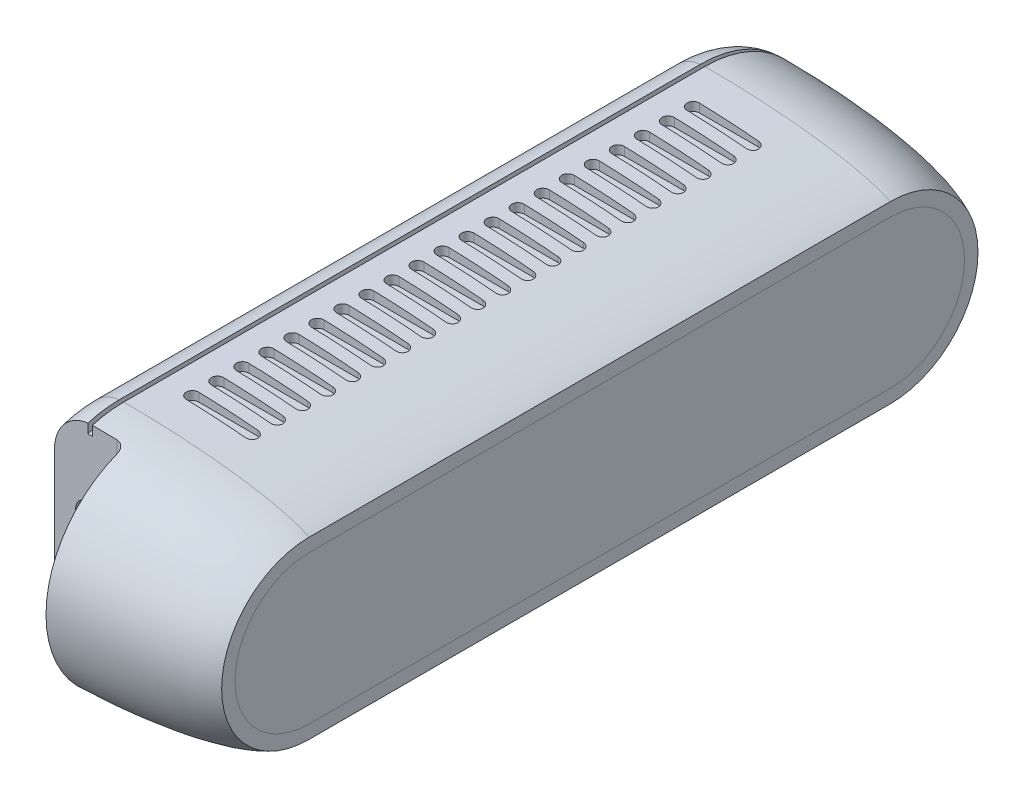
SolidWorks part; units mm, degrees
ref_plane "Front Plane" through (0, 0, 0) normal (0, 0, 1) x (1, 0, 0)
ref_plane "Top Plane" through (0, 0, 0) normal (0, 1, 0) x (1, 0, 0)
ref_plane "Right Plane" through (0, 0, 0) normal (1, 0, 0) x (0, 0, -1)
sketch "Sketch1" plane through (0, 0, 0) normal (0, 0, 1) x (1, 0, 0)
  line L0 (0, 0) -> (0, 8.25)
  line L1 (25, 9.7958) -> (25, 0)
  line L2 (25, 0) -> (0, 0)
  line L3 (4.25, 12.5) -> (4.25, 11.4705)
  line L4 (4.25, 11.4705) -> (3.75, 11.4705)
  line L5 (3.75, 11.4705) -> (3.75, 12.4705)
  arc A0 (0, 8.25) -> (3.75, 12.4705) centre (4.25, 8.25) cw
  arc A1 (4.25, 12.5) -> (3.75, 12.4705) centre (4.25, 8.25) ccw construction
  ellipse E0 centre (4.25, 8.25) end of major axis (26.5257, 8.25) minor radius 4.25 (4.25, 12.5) -> (25, 9.7958) cw
  point P4 (0, 0)
  dimension "D1" = 12.5
  dimension "D2" = 8.25
  dimension "D3" = 0.5
  dimension "D4" = 1
  dimension "D5" = 25
  dimension "D6" = 9.7958
extrude "Boss-Extrude1" add sketch "Sketch1" along normal blind 32.5
sketch "Sketch5" plane through (0, 0, 32.5) normal (0, 0, 1) x (1, 0, 0)
  line L6 (0, 0) -> (25, 0)
  line L7 (25, 0) -> (25, 9.7958)
  line L8 (4.25, 12.5) -> (4.25, 11.4705)
  line L9 (4.25, 11.4705) -> (3.75, 11.4705)
  line L10 (3.75, 11.4705) -> (3.75, 12.4705)
  line L11 (0, 8.25) -> (0, 0)
  line L12 (0, 0) -> (25, 0)
  line L13 (25, 0) -> (25, 9.7958)
  line L14 (4.25, 12.5) -> (4.25, 11.4705)
  line L15 (4.25, 11.4705) -> (3.75, 11.4705)
  line L16 (3.75, 11.4705) -> (3.75, 12.4705)
  line L17 (0, 8.25) -> (0, 0)
  arc A1 (3.75, 12.4705) -> (0, 8.25) centre (4.25, 8.25) ccw
  arc A2 (3.75, 12.4705) -> (0, 8.25) centre (4.25, 8.25) ccw
  ellipse E1 centre (4.25, 8.25) end of major axis (26.5257, 8.25) minor radius 4.25 (25, 9.7958) -> (4.25, 12.5) ccw
  ellipse E2 centre (4.25, 8.25) end of major axis (26.5257, 8.25) minor radius 4.25 (25, 9.7958) -> (4.25, 12.5) ccw
  dimension "D1" = 0
revolve "Revolve1" add sketch "Sketch5" angle 90 about L12
mirror "Mirror1" about plane through (4.25, 8.25, 0) normal (0, 0, -1) of bodies 102
mirror "Mirror2" about plane through (25, 0, 32.5) normal (0, 1, 0) of bodies 103
sketch "Sketch6" plane through (0, 0, 0) normal (-1, 0, 0) x (0, 0, 1)
  line L0 (-22.5, 0) -> (0, 0) construction
  line L1 (0, 0) -> (22.5, 0) construction
  point P3 (-22.5, 0)
  point P4 (22.5, 0)
  dimension "D1" = 45
hole_wizard "Ø3.0mm Dowel Hole1" positions "Sketch9" profile "Sketch11" hole size "Ø3.0" standard "ANSI Metric"
sketch "Sketch9" plane through (0, 0, 0) normal (-1, 0, 0) x (0, 0, 1)
  point P0 (-22.5, 0)
  point P3 (22.5, 0)
sketch "Sketch11" plane through (0, 0, -22.5) normal (0, 1, 0) x (0, 0, 1)
  line L0 (0, 0) -> (0, 3.25)
  line L1 (0, 3.25) -> (1.5, 2.3487)
  line L2 (1.5, 2.3487) -> (1.5, 0)
  line L5 (1.5, 0) -> (0, 0)
  line L10 (0, 3.25) -> (-1.5, 2.3487) construction
  line L11 (0, -6.35) -> (0, 107.95) construction
  dimension "Hole Dia." = 3
  dimension "Hole Depth" = 3.25
  dimension "Drill Angle" = 118
sketch "Sketch12" plane through (25, 0, 0) normal (1, 0, 0) x (0, 0, -1)
  line L0 (32.5, 8.2958) -> (-32.5, 8.2958)
  line L1 (-32.5, -8.2958) -> (32.5, -8.2958)
  line L2 (-32.5, -9.7958) -> (32.5, -9.7958)
  line L3 (32.5, 9.7958) -> (-32.5, 9.7958)
  line L4 (-32.5, -9.7958) -> (32.5, -9.7958) construction
  line L5 (32.5, 9.7958) -> (-32.5, 9.7958) construction
  arc A0 (-32.5, 8.2958) -> (-32.5, -8.2958) centre (-32.5, 0) ccw
  arc A1 (32.5, -8.2958) -> (32.5, 8.2958) centre (32.5, 0) ccw
  arc A2 (-32.5, 9.7958) -> (-32.5, -9.7958) centre (-32.5, 0) ccw
  arc A3 (32.5, -9.7958) -> (32.5, 9.7958) centre (32.5, 0) ccw
  arc A4 (-32.5, 9.7958) -> (-32.5, -9.7958) centre (-32.5, 0) ccw construction
  arc A5 (32.5, -9.7958) -> (32.5, 9.7958) centre (32.5, 0) ccw construction
  dimension "D1" = 0
  dimension "D2" = 1.5
split line "Split Line1"
sketch "Sketch13" plane through (0, 0, 0) normal (0, 1, 0) x (1, 0, 0)
  line L0 (0, -32.5) -> (0, 32.5) construction
  line L1 (8, -36) -> (0, -36)
  line L2 (8, -36) -> (8, -45)
  line L3 (8, -45) -> (0, -45)
  line L4 (0, -36) -> (0, -45)
  dimension "D1" = 8
  dimension "D2" = 9
extrude "Cut-Extrude1" cut sketch "Sketch13" against normal through all both and the other way through all
fillet "Fillet1" radius 1 1 edges at (8, 0, 36)
ref_plane "Plane2" through (0, 12.5, 0) normal (0, 1, 0) x (1, 0, 0)
sketch "Sketch15" plane through (0, 12.5, 0) normal (0, 1, 0) x (1, 0, 0)
  line L0 (14.05, 0) -> (7.45, 0) construction
  line L1 (14.05, -0.7) -> (7.45, -0.7)
  line L2 (14.05, 0.7) -> (7.45, 0.7)
  line L3 (4.25, -32.5) -> (4.25, 32.5) construction
  line L4 (14.05, 2.8) -> (7.45, 2.8) construction
  line L5 (14.05, 2.1) -> (7.45, 2.1)
  line L6 (14.05, 3.5) -> (7.45, 3.5)
  line L7 (14.05, 5.6) -> (7.45, 5.6) construction
  line L8 (14.05, 4.9) -> (7.45, 4.9)
  line L9 (14.05, 6.3) -> (7.45, 6.3)
  line L10 (14.05, 8.4) -> (7.45, 8.4) construction
  line L11 (14.05, 7.7) -> (7.45, 7.7)
  line L12 (14.05, 9.1) -> (7.45, 9.1)
  line L13 (14.05, 11.2) -> (7.45, 11.2) construction
  line L14 (14.05, 10.5) -> (7.45, 10.5)
  line L15 (14.05, 11.9) -> (7.45, 11.9)
  line L16 (14.05, 14) -> (7.45, 14) construction
  line L17 (14.05, 13.3) -> (7.45, 13.3)
  line L18 (14.05, 14.7) -> (7.45, 14.7)
  line L19 (14.05, 16.8) -> (7.45, 16.8) construction
  line L20 (14.05, 16.1) -> (7.45, 16.1)
  line L21 (14.05, 17.5) -> (7.45, 17.5)
  line L22 (14.05, 19.6) -> (7.45, 19.6) construction
  line L23 (14.05, 18.9) -> (7.45, 18.9)
  line L24 (14.05, 20.3) -> (7.45, 20.3)
  line L25 (14.05, 22.4) -> (7.45, 22.4) construction
  line L26 (14.05, 21.7) -> (7.45, 21.7)
  line L27 (14.05, 23.1) -> (7.45, 23.1)
  line L28 (14.05, 25.2) -> (7.45, 25.2) construction
  line L29 (14.05, 24.5) -> (7.45, 24.5)
  line L30 (14.05, 25.9) -> (7.45, 25.9)
  line L31 (14.05, 28) -> (7.45, 28) construction
  line L32 (14.05, 27.3) -> (7.45, 27.3)
  line L33 (14.05, 28.7) -> (7.45, 28.7)
  line L34 (14.05, -2.8) -> (7.45, -2.8) construction
  line L35 (14.05, -3.5) -> (7.45, -3.5)
  line L36 (14.05, -2.1) -> (7.45, -2.1)
  line L37 (14.05, -5.6) -> (7.45, -5.6) construction
  line L38 (14.05, -6.3) -> (7.45, -6.3)
  line L39 (14.05, -4.9) -> (7.45, -4.9)
  line L40 (14.05, -8.4) -> (7.45, -8.4) construction
  line L41 (14.05, -9.1) -> (7.45, -9.1)
  line L42 (14.05, -7.7) -> (7.45, -7.7)
  line L43 (14.05, -11.2) -> (7.45, -11.2) construction
  line L44 (14.05, -11.9) -> (7.45, -11.9)
  line L45 (14.05, -10.5) -> (7.45, -10.5)
  line L46 (14.05, -14) -> (7.45, -14) construction
  line L47 (14.05, -14.7) -> (7.45, -14.7)
  line L48 (14.05, -13.3) -> (7.45, -13.3)
  line L49 (14.05, -16.8) -> (7.45, -16.8) construction
  line L50 (14.05, -17.5) -> (7.45, -17.5)
  line L51 (14.05, -16.1) -> (7.45, -16.1)
  line L52 (14.05, -19.6) -> (7.45, -19.6) construction
  line L53 (14.05, -20.3) -> (7.45, -20.3)
  line L54 (14.05, -18.9) -> (7.45, -18.9)
  line L55 (14.05, -22.4) -> (7.45, -22.4) construction
  line L56 (14.05, -23.1) -> (7.45, -23.1)
  line L57 (14.05, -21.7) -> (7.45, -21.7)
  line L58 (14.05, -25.2) -> (7.45, -25.2) construction
  line L59 (14.05, -25.9) -> (7.45, -25.9)
  line L60 (14.05, -24.5) -> (7.45, -24.5)
  line L61 (14.05, -28) -> (7.45, -28) construction
  line L62 (14.05, -28.7) -> (7.45, -28.7)
  line L63 (14.05, -27.3) -> (7.45, -27.3)
  arc A0 (14.05, -0.7) -> (14.05, 0.7) centre (14.05, 0) ccw
  arc A1 (7.45, 0.7) -> (7.45, -0.7) centre (7.45, 0) ccw
  arc A2 (14.05, 2.1) -> (14.05, 3.5) centre (14.05, 2.8) ccw
  arc A3 (7.45, 3.5) -> (7.45, 2.1) centre (7.45, 2.8) ccw
  arc A4 (14.05, 4.9) -> (14.05, 6.3) centre (14.05, 5.6) ccw
  arc A5 (7.45, 6.3) -> (7.45, 4.9) centre (7.45, 5.6) ccw
  arc A6 (14.05, 7.7) -> (14.05, 9.1) centre (14.05, 8.4) ccw
  arc A7 (7.45, 9.1) -> (7.45, 7.7) centre (7.45, 8.4) ccw
  arc A8 (14.05, 10.5) -> (14.05, 11.9) centre (14.05, 11.2) ccw
  arc A9 (7.45, 11.9) -> (7.45, 10.5) centre (7.45, 11.2) ccw
  arc A10 (14.05, 13.3) -> (14.05, 14.7) centre (14.05, 14) ccw
  arc A11 (7.45, 14.7) -> (7.45, 13.3) centre (7.45, 14) ccw
  arc A12 (14.05, 16.1) -> (14.05, 17.5) centre (14.05, 16.8) ccw
  arc A13 (7.45, 17.5) -> (7.45, 16.1) centre (7.45, 16.8) ccw
  arc A14 (14.05, 18.9) -> (14.05, 20.3) centre (14.05, 19.6) ccw
  arc A15 (7.45, 20.3) -> (7.45, 18.9) centre (7.45, 19.6) ccw
  arc A16 (14.05, 21.7) -> (14.05, 23.1) centre (14.05, 22.4) ccw
  arc A17 (7.45, 23.1) -> (7.45, 21.7) centre (7.45, 22.4) ccw
  arc A18 (14.05, 24.5) -> (14.05, 25.9) centre (14.05, 25.2) ccw
  arc A19 (7.45, 25.9) -> (7.45, 24.5) centre (7.45, 25.2) ccw
  arc A20 (14.05, 27.3) -> (14.05, 28.7) centre (14.05, 28) ccw
  arc A21 (7.45, 28.7) -> (7.45, 27.3) centre (7.45, 28) ccw
  arc A22 (14.05, -3.5) -> (14.05, -2.1) centre (14.05, -2.8) ccw
  arc A23 (7.45, -2.1) -> (7.45, -3.5) centre (7.45, -2.8) ccw
  arc A24 (14.05, -6.3) -> (14.05, -4.9) centre (14.05, -5.6) ccw
  arc A25 (7.45, -4.9) -> (7.45, -6.3) centre (7.45, -5.6) ccw
  arc A26 (14.05, -9.1) -> (14.05, -7.7) centre (14.05, -8.4) ccw
  arc A27 (7.45, -7.7) -> (7.45, -9.1) centre (7.45, -8.4) ccw
  arc A28 (14.05, -11.9) -> (14.05, -10.5) centre (14.05, -11.2) ccw
  arc A29 (7.45, -10.5) -> (7.45, -11.9) centre (7.45, -11.2) ccw
  arc A30 (14.05, -14.7) -> (14.05, -13.3) centre (14.05, -14) ccw
  arc A31 (7.45, -13.3) -> (7.45, -14.7) centre (7.45, -14) ccw
  arc A32 (14.05, -17.5) -> (14.05, -16.1) centre (14.05, -16.8) ccw
  arc A33 (7.45, -16.1) -> (7.45, -17.5) centre (7.45, -16.8) ccw
  arc A34 (14.05, -20.3) -> (14.05, -18.9) centre (14.05, -19.6) ccw
  arc A35 (7.45, -18.9) -> (7.45, -20.3) centre (7.45, -19.6) ccw
  arc A36 (14.05, -23.1) -> (14.05, -21.7) centre (14.05, -22.4) ccw
  arc A37 (7.45, -21.7) -> (7.45, -23.1) centre (7.45, -22.4) ccw
  arc A38 (14.05, -25.9) -> (14.05, -24.5) centre (14.05, -25.2) ccw
  arc A39 (7.45, -24.5) -> (7.45, -25.9) centre (7.45, -25.2) ccw
  arc A40 (14.05, -28.7) -> (14.05, -27.3) centre (14.05, -28) ccw
  arc A41 (7.45, -27.3) -> (7.45, -28.7) centre (7.45, -28) ccw
  point P2 (10.75, 0)
  point P8 (14.75, 0)
  point P9 (6.75, 0)
  point P15 (10.75, 2.8)
  point P22 (10.75, 5.6)
  point P29 (10.75, 8.4)
  point P36 (10.75, 11.2)
  point P43 (10.75, 14)
  point P50 (10.75, 16.8)
  point P57 (10.75, 19.6)
  point P64 (10.75, 22.4)
  point P71 (10.75, 25.2)
  point P78 (10.75, 28)
  point P86 (10.75, -2.8)
  point P93 (10.75, -5.6)
  point P100 (10.75, -8.4)
  point P107 (10.75, -11.2)
  point P114 (10.75, -14)
  point P121 (10.75, -16.8)
  point P128 (10.75, -19.6)
  point P135 (10.75, -22.4)
  point P142 (10.75, -25.2)
  point P149 (10.75, -28)
  dimension "D1" = 8
  dimension "D2" = 1.4
  dimension "D3" = 2.5
  dimension "D4" = 11
  dimension "D5" = 11
extrude "Cut-Extrude2" cut sketch "Sketch15" against normal blind 1
sketch "Sketch16" plane through (0, 0, 36) normal (0, 0, 1) x (1, 0, 0)
  line L0 (3.87, 2.925) -> (3.87, -2.925) construction
  line L1 (5.37, 2.925) -> (5.37, -2.925)
  line L2 (2.37, 2.925) -> (2.37, -2.925)
  line L3 (0, -7.4708) -> (0, 7.4708) construction
  arc A0 (5.37, 2.925) -> (2.37, 2.925) centre (3.87, 2.925) ccw
  arc A1 (2.37, -2.925) -> (5.37, -2.925) centre (3.87, -2.925) ccw
  point P2 (3.87, 0)
  point P7 (4.5, 5.925)
  point P10 (0, 0)
  point P11 (3.87, 4.425)
  point P12 (3.87, -4.425)
  point P13 (0, 0)
  dimension "D1" = 8.85
  dimension "D2" = 3
  dimension "D3" = 2.37
extrude "Cut-Extrude3" cut sketch "Sketch16" against normal blind 5
ref_plane "Plane3" through (0, -12.5, 0) normal (0, -1, 0) x (-1, 0, 0)
sketch "Sketch17" plane through (0, -12.5, 0) normal (0, -1, 0) x (-1, 0, 0)
  line L0 (-4.25, -30.5) -> (-12.042, -29.25)
  line L1 (-16.25, -24.3132) -> (-16.25, 24.3132)
  line L2 (-12.042, 29.25) -> (-4.25, 30.5)
  line L5 (-4.25, -30.5) -> (-4.25, 30.5)
  line L6 (-4.25, 0) -> (-16.25, 0) construction
  line L7 (-4.25, -32.5) -> (-4.25, 32.5) construction
  arc A0 (-12.042, 29.25) -> (-16.25, 24.3132) centre (-11.25, 24.3132) ccw
  arc A1 (-16.25, -24.3132) -> (-12.042, -29.25) centre (-11.25, -24.3132) ccw
  point P9 (-4.25, 0)
  point P12 (-16.25, 28.575)
  point P15 (-16.25, -28.575)
  dimension "D4" = 5
  dimension "D1" = 61
  dimension "D2" = 57.15
  dimension "D3" = 12
extrude "Boss-Extrude2" add sketch "Sketch17" against normal up to next
sketch "Sketch18" plane through (0, -12.5, 0) normal (0, -1, 0) x (1, 0, 0)
  line L0 (4.25, 0) -> (9.6475, 0) construction
  line L1 (4.25, 30.5) -> (4.25, -30.5) construction
  point P6 (9.6475, 0)
  dimension "D1" = 5.3975
hole_wizard "1/4 (0.25) Diameter Hole1" positions "Sketch19" profile "Sketch20" hole size "1/4" standard "ANSI Inch"
sketch "Sketch19" plane through (0, -12.5, 0) normal (0, -1, 0) x (-1, 0, 0)
  point P0 (-9.6475, 0)
sketch "Sketch20" plane through (9.6475, -12.5, 0) normal (1, 0, 0) x (0, 0, -1)
  line L0 (0, 0) -> (0, 9.906)
  line L1 (0, 9.906) -> (3.175, 7.9983)
  line L2 (3.175, 7.9983) -> (3.175, 0)
  line L5 (3.175, 0) -> (0, 0)
  line L10 (0, 9.906) -> (-3.175, 7.9983) construction
  line L11 (0, -6.35) -> (0, 107.95) construction
  dimension "Hole Dia." = 6.35
  dimension "Hole Depth" = 9.906
  dimension "Drill Angle" = 118
thread "Thread1" pitch 1.27 method extrude profile "Thread Profile1" start angle 0, offset 0, length 0, pitch 1.27, diameter 6.35
ref_plane "Plane4" through (12.8225, -12.5, 0) normal (0, 0, 1) x (1, 0, 0)
sketch "Thread Profile1" plane through (12.8225, -12.5, 0) normal (0, 0, 1) x (1, 0, 0)
  line L0 (0, 0) -> (0, 1.27) construction
  line L11 (0, 0) -> (0, 1.1112)
  line L12 (0, 1.1112) -> (-0.6874, 0.7144)
  line L13 (-0.6874, 0.7144) -> (-0.6874, 0.3969)
  line L15 (-0.6874, 0.3969) -> (0, 0)
  line L17 (-0.6874, 0.5556) -> (0, 0.5556) construction
  point P2 (0, 0)
  dimension "Pitch" = 1.27
  dimension "Profile_Angle" = 60
  dimension "Profile_Land" = 0.3175
  dimension "Profile_Height" = 0.6874
extrude "Cut-Extrude4" cut sketch "Sketch15<2>" along normal blind 1 from surface contours L29 A19 L30 A18 | L26 A17 L27 A16 | L23 A15 L24 A14 | L20 A13 L21 A12 | L17 A11 L18 A10 | L14 A9 L15 A8 | L11 A7 L12 A6 | L8 A5 L9 A4 | L38 A25 L39 A24 | L41 A27 L42 A26 | L44 A29 L45 A28 | L47 A31 L48 A30 | L50 A33 L51 A32 | L53 A35 L54 A34 | L56 A37 L57 A36 | L59 A39 L60 A38 starting at face at (9.6475, -12.5, -3.175)
sketch "Sketch15<2>" plane through (0, 12.5, 0) normal (0, 1, 0) x (1, 0, 0) same geometry as "Sketch15"
